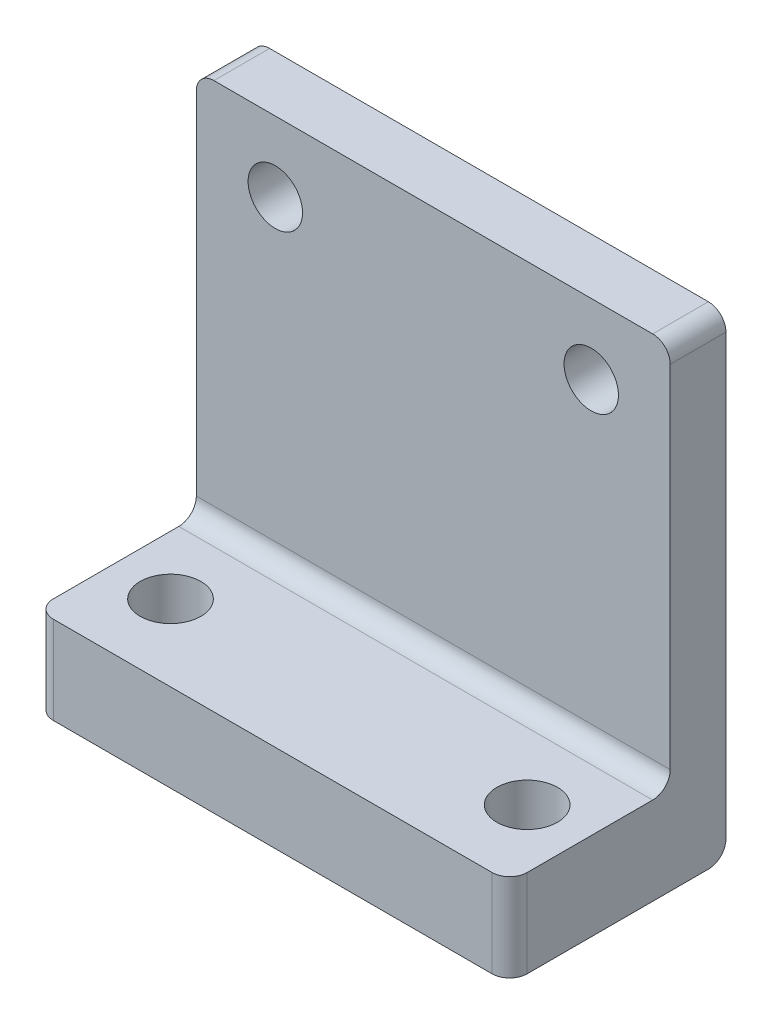
SolidWorks part; units mm, degrees
ref_plane "Front Plane" through (0, 0, 0) normal (0, 0, 1) x (1, 0, 0)
ref_plane "Top Plane" through (0, 0, 0) normal (0, 1, 0) x (1, 0, 0)
ref_plane "Right Plane" through (0, 0, 0) normal (1, 0, 0) x (0, 0, -1)
sketch "Sketch1" plane through (0, 0, 0) normal (0, 0, 1) x (1, 0, 0)
  line L0 (0, -20) -> (27, -20)
  line L1 (0, 0) -> (27, 0)
  line L2 (0, 0) -> (0, -25)
  line L3 (0, -25) -> (27, -25)
  line L4 (27, 0) -> (27, -25)
  line L5 (0, 0) -> (0, 2)
  line L6 (0, 2) -> (27, 2)
  line L7 (27, 2) -> (27, 0)
  circle A0 centre (4.5, -2) radius 1.55
  circle A1 centre (22.5, -2) radius 1.55
  dimension "D2" = 3.1
  dimension "D1" = 18
  dimension "D4" = 5
  dimension "D5" = 27
  dimension "D6" = 4.5
  dimension "D7" = 2
  dimension "D3" = 20
  dimension "D8" = 2
extrude "Boss-Extrude1" add sketch "Sketch1" along normal blind 3.175 contours L4 L1 L2 L0 A1 A0 | L4 L0 L2 L3 | L7 L6 L5 L1 region at (13.5, -10.2301, 0) region at (13.5, -22.5, 0) region at (13.5, 1, 0)
extrude "Boss-Extrude2" add sketch "Sketch1<3>" along normal blind 9.15 from surface contours L4 L0 L2 L3 region at (13.5, -22.5, 0) starting at face at (24.05, -2, 3.175)
sketch "Sketch1<3>" plane through (0, 0, 0) normal (0, 0, 1) x (1, 0, 0) same geometry as "Sketch1"
sketch "Mount Hole Location" plane through (0, -20, 0) normal (0, 1, 0) x (1, 0, 0)
  line L0 (0, -12.325) -> (27, -12.325) construction
  line L1 (5.626, -7.985) -> (21.374, -7.985) construction
  line L2 (0, -3.175) -> (27, -3.175) construction
  line L3 (0, -4.959) -> (27, -4.959) construction
  line L4 (0, -12.325) -> (0, -3.175) construction
  line L5 (27, -12.325) -> (27, -3.175) construction
  line L6 (27, -12.325) -> (0, -12.325) construction
  line L7 (3.34, -5.699) -> (3.34, -4.959) construction
  circle A0 centre (23.66, -7.985) radius 3.4925 construction
  circle A1 centre (23.66, -7.985) radius 2.286
  circle A2 centre (3.34, -7.985) radius 2.286
  circle A3 centre (3.34, -7.985) radius 3.4925 construction
  point P0 (13.5, -7.985)
  point P4 (13.5, -12.325)
  point P15 (13.5, -7.985)
  point P23 (0, 0)
  point P24 (22.86, -6.7398)
  dimension "D2" = 6.985
  dimension "D3" = 4.572
  dimension "D1" = 4.81
  dimension "D4" = 20.32
  dimension "D5" = 7.366
hole_wizard "#8-32 Tapped Hole1" positions "3DSketch1" profile "Sketch3" tap size "#8-32" standard "ANSI Inch" end condition through all
sketch3d "3DSketch1"
  point P5 (3.34, -20, 7.985)
  point P8 (23.66, -20, 7.985)
sketch "Sketch3" plane through (3.34, -20, 7.985) normal (1, 0, 0) x (0, 0, 1)
  line L0 (0, 0) -> (0, 5)
  line L1 (0, 5) -> (1.7272, 5)
  line L2 (1.7272, 5) -> (1.7272, 0)
  line L5 (1.7272, 0) -> (0, 0)
  line L11 (0, -6.35) -> (0, 107.95) construction
  dimension "Thru Tap Drill Dia." = 3.4544
  dimension "Thru Tap Drill Depth" = 5
cosmetic thread "Hole Thread1"
cosmetic thread "Hole Thread2"
fillet "Fillet1" radius 1 6 edges at (0, -22.5, 12.325) (27, -22.5, 12.325) (13.5, -25, 0) (13.5, -20, 3.175) (27, 2, 1.5875) (0, 2, 1.5875)
sketch "Sketch4" plane through (0, -20, 0) normal (0, 1, 0) x (1, 0, 0)
  circle A0 centre (3.34, -7.985) radius 2.465
  circle A1 centre (23.66, -7.985) radius 2.465
  dimension "D1" = 4.93
  dimension "D2" = 4.93
equation "\"D6@Sketch1\"=(\"D5@Sketch1\"-\"D1@Sketch1\")/2"
